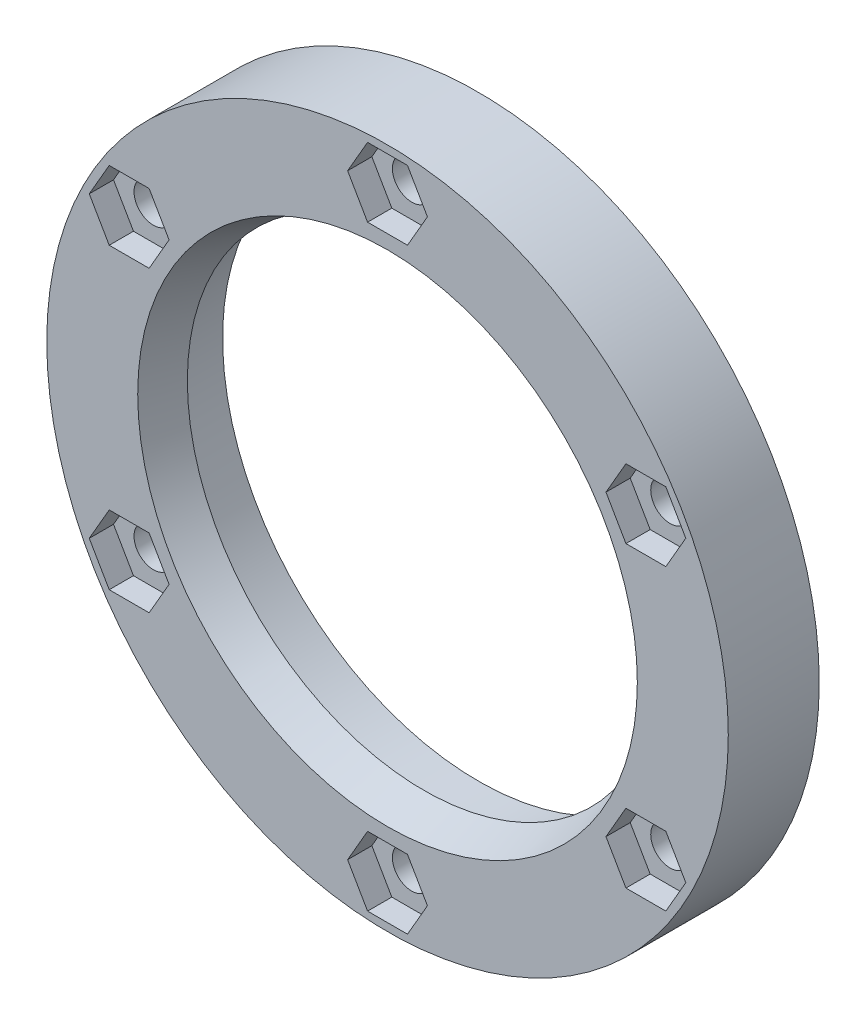
SolidWorks part; units mm, degrees
material "PPE"
ref_plane "Front Plane" through (0, 0, 0) normal (0, 0, 1) x (1, 0, 0)
ref_plane "Top Plane" through (0, 0, 0) normal (0, 1, 0) x (1, 0, 0)
ref_plane "Right Plane" through (0, 0, 0) normal (1, 0, 0) x (0, 0, -1)
sketch "Sketch1" plane through (0, 0, 0) normal (0, 0, 1) x (1, 0, 0)
  circle A0 centre (0, 0) radius 21.1
  circle A1 centre (0, 0) radius 28.1
  dimension "D1" = 42.2
  dimension "D2" = 7
extrude "Boss-Extrude1" add sketch "Sketch1" along normal blind 4.5
sketch "Sketch2" plane through (0, 0, 4.5) normal (0, 0, 1) x (1, 0, 0)
  circle A0 centre (0, 0) radius 18.6
  circle A1 centre (0, 0) radius 28.1
  circle A2 centre (0, 0) radius 21.1 construction
  circle A3 centre (0, 0) radius 28.1 construction
  dimension "D1" = 2.5
extrude "Boss-Extrude2" add sketch "Sketch2" along normal blind 3
hole_wizard "M3 Clearance Hole1" positions "Sketch3" profile "Sketch4" hole size "M3" standard "ANSI Metric" end condition through all
sketch "Sketch3" plane through (0, 0, 0) normal (0, 0, -1) x (-1, 0, 0)
  line L0 (0, 0) -> (0, 21.1) construction
  line L1 (0, 21.1) -> (0, 24.6) construction
  line L2 (0, 24.6) -> (0, 28.1) construction
  circle A0 centre (0, 0) radius 21.1 construction
  circle A1 centre (0, 0) radius 28.1 construction
  point P0 (0, 24.6)
sketch "Sketch4" plane through (0, 24.6, 0) normal (1, 0, 0) x (0, 1, 0)
  line L0 (0, 0) -> (0, 7.5)
  line L1 (0, 7.5) -> (1.6, 7.5)
  line L2 (1.6, 7.5) -> (1.6, 0)
  line L5 (1.6, 0) -> (0, 0)
  line L11 (0, -6.35) -> (0, 107.95) construction
  dimension "Thru Hole Dia." = 3.2
  dimension "Thru Hole Depth" = 7.5
sketch "Sketch5" plane through (0, 0, 7.5) normal (0, 0, 1) x (1, 0, 0)
  line L0 (-1.6454, 27.45) -> (1.6454, 27.45)
  line L1 (1.6454, 27.45) -> (3.2909, 24.6)
  line L2 (3.2909, 24.6) -> (1.6454, 21.75)
  line L3 (1.6454, 21.75) -> (-1.6454, 21.75)
  line L4 (-1.6454, 21.75) -> (-3.2909, 24.6)
  line L5 (-3.2909, 24.6) -> (-1.6454, 27.45)
  circle A0 centre (0, 24.6) radius 2.85 construction
  dimension "D1" = 5.7
extrude "Cut-Extrude1" cut sketch "Sketch5" against normal blind 2
pattern_circular "CirPattern1" count 6 over 360 about axis through (0, 0, 4.5) along (0, 0, -1) of "M3 Clearance Hole1", "Cut-Extrude1" reverse direction yes
chamfer "Chamfer1" distance 2 angle 70 1 edges at (18.6, 0, 7.5) first distance on face at (21.3042, 12.3, 7.5)
